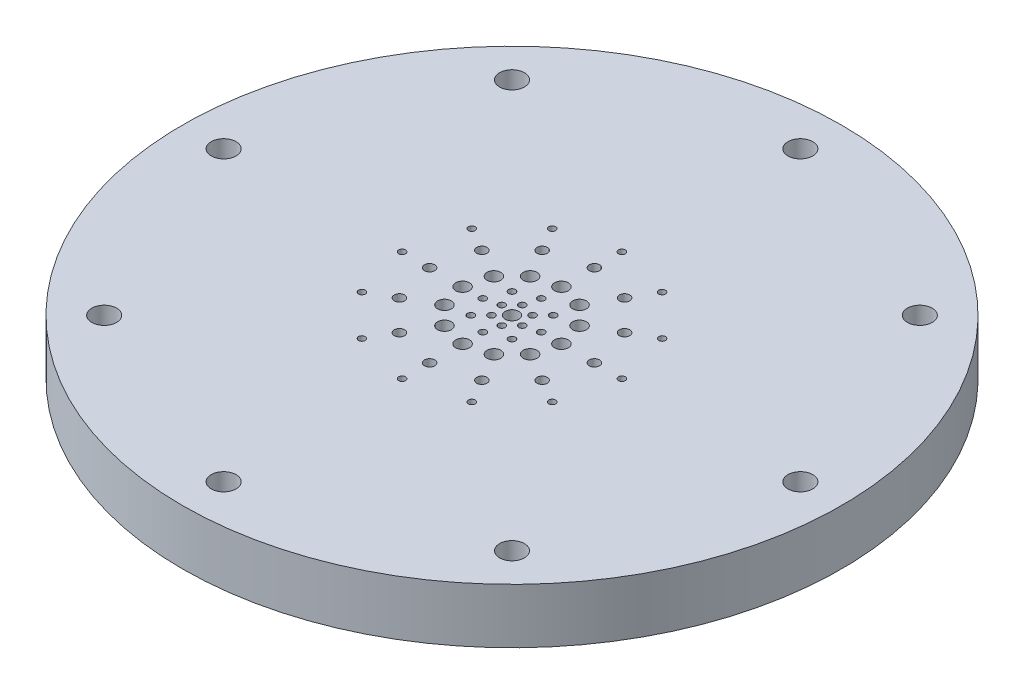
SolidWorks part; units mm, degrees
ref_plane "Front Plane" through (0, 0, 0) normal (0, 0, 1) x (1, 0, 0)
ref_plane "Top Plane" through (0, 0, 0) normal (0, 1, 0) x (1, 0, 0)
ref_plane "Right Plane" through (0, 0, 0) normal (1, 0, 0) x (0, 0, -1)
sketch "Sketch1" plane through (0, 0, 0) normal (0, 1, 0) x (1, 0, 0)
  circle A0 centre (0, 0) radius 38.1
  dimension "D1" = 76.2
extrude "Boss-Extrude1" add sketch "Sketch1" along normal blind 6.35
sketch "Sketch2" plane through (0, 0, 0) normal (0, -1, 0) x (1, 0, 0)
  circle A0 centre (0, 0) radius 33.3375
  circle A1 centre (0, 33.3375) radius 0.762
  dimension "D1" = 66.675
hole_wizard "CBORE for #4 Button Head Cap Screw1" positions "Sketch5" profile "Sketch4" counterbore size "#4" standard "ANSI Inch" end condition through all
sketch "Sketch5" plane through (0, 0, 0) normal (0, -1, 0) x (-1, 0, 0)
  point P0 (0, -33.3375)
sketch "Sketch4" plane through (0, 0, 33.3375) normal (1, 0, 0) x (0, 0, -1)
  line L0 (0, 0) -> (0, 6.35)
  line L1 (0, 6.35) -> (1.4351, 6.35)
  line L3 (1.4351, 6.35) -> (1.4351, 1.905)
  line L4 (1.4351, 1.905) -> (2.413, 1.905)
  line L5 (2.413, 1.905) -> (2.413, 0)
  line L7 (2.413, 0) -> (0, 0)
  line L11 (0, -6.35) -> (0, 107.95) construction
  dimension "Thru Hole Dia." = 2.8702
  dimension "Thru Hole Depth" = 6.35
  dimension "C'Bore Dia." = 4.826
  dimension "C'Bore Depth" = 1.905
pattern_circular "CirPattern1" count 8 over 360 about axis through (0, 0, 0) along (0, 1, 0) of "CBORE for #4 Button Head Cap Screw1"
sketch "Sketch6" plane through (0, 6.35, 0) normal (0, 1, 0) x (1, 0, 0)
  circle A0 centre (0, 0) radius 28.575
  dimension "D1" = 57.15
sketch "Sketch7" plane through (0, 0, 0) normal (0, -1, 0) x (1, 0, 0)
  circle A0 centre (0, 12.7) radius 0.3937
  circle A1 centre (0, 9.525) radius 0.5969
  circle A2 centre (0, 5.715) radius 0.8001
  circle A3 centre (0, 0) radius 0.7937
  dimension "D1" = 0.7874
  dimension "D3" = 1.1938
  dimension "D4" = 9.525
  dimension "D5" = 1.6002
  dimension "D6" = 5.715
  dimension "D7" = 1.5875
  dimension "D2" = 12.7
extrude "Cut-Extrude1" cut sketch "Sketch7" against normal through all
pattern_circular "CirPattern3" count 12 over 360 about axis through (0, 0, 0) along (0, 1, 0) of "Cut-Extrude1"
sketch "Sketch8" plane through (0, 6.35, 0) normal (0, 1, 0) x (1, 0, 0)
  circle A0 centre (3.3688, 0) radius 0.3969
  circle A1 centre (2.3821, -2.3821) radius 0.3969
  circle A2 centre (0, -3.3688) radius 0.3969
  circle A3 centre (-2.3821, -2.3821) radius 0.3969
  circle A4 centre (-3.3688, 0) radius 0.3969
  circle A5 centre (-2.3821, 2.3821) radius 0.3969
  circle A6 centre (0, 3.3688) radius 0.3969
  circle A7 centre (2.3821, 2.3821) radius 0.3969
  point P19 (0, 0)
  dimension "D1" = 8
extrude "Cut-Extrude3" cut sketch "Sketch8" against normal up to next
sketch "Sketch9" plane through (0, 6.35, 0) normal (0, 1, 0) x (1, 0, 0)
  line L0 (0, 0) -> (2.3821, 2.3821) construction
  circle A2 centre (1.1877, 1.1877) radius 0.3969
  circle A3 centre (1.6225, -0.4347) radius 0.3969
  circle A4 centre (0.4347, -1.6225) radius 0.3969
  circle A5 centre (-1.1877, -1.1877) radius 0.3969
  circle A6 centre (-1.6225, 0.4347) radius 0.3969
  circle A7 centre (-0.4347, 1.6225) radius 0.3969
  point P18 (0, 0)
  dimension "D1" = 1.6891
  dimension "D2" = 6
extrude "Cut-Extrude4" cut sketch "Sketch9" against normal up to next
